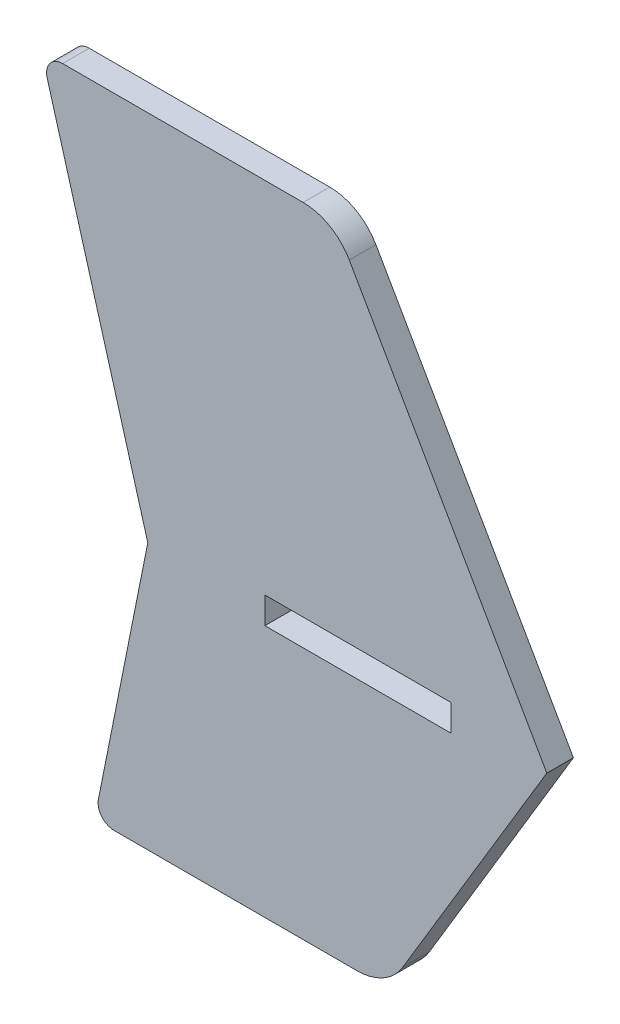
SolidWorks part; units mm, degrees
ref_plane "Ebene vorne" through (0, 0, 0) normal (0, 0, 1) x (1, 0, 0)
ref_plane "Ebene oben" through (0, 0, 0) normal (0, 1, 0) x (1, 0, 0)
ref_plane "Ebene rechts" through (0, 0, 0) normal (1, 0, 0) x (0, 0, -1)
sketch "Skizze1" plane through (0, 0, 0) normal (0, 0, 1) x (1, 0, 0)
  line L1 (-35, 120) -> (20, 120)
  line L2 (20, 120) -> (60, 50)
  line L3 (60, 50) -> (30, 0)
  line L4 (30, 0) -> (0, 0)
  line L5 (-35, 120) -> (-15, 50)
  line L6 (-15, 50) -> (-25, 0)
  line L7 (-25, 0) -> (0, 0)
  dimension "D1" = 120
  dimension "D2" = 55
  dimension "D3" = 30
  dimension "D4" = 40
  dimension "D5" = 50
  dimension "D6" = 30
  dimension "D7" = 25
  dimension "D8" = 75
extrude "Grundplatte" add sketch "Skizze1" along normal blind 5 contours L1 L2 L3 L4 L7 L6 L5
sketch "Skizze2" plane through (0, 0, 5) normal (0, 0, 1) x (1, 0, 0)
  line L1 (7, 47.5) -> (42, 47.5)
  line L2 (7, 47.5) -> (7, 52.5)
  line L3 (7, 52.5) -> (42, 52.5)
  line L4 (42, 47.5) -> (42, 52.5)
  line L5 (42, 50) -> (60, 50) construction
  dimension "D1" = 35
  dimension "D2" = 5
  dimension "D3" = 18
extrude "NutHöhenleitwerk" cut sketch "Skizze2" against normal blind 15
fillet "Verrundung1" radius 10 2 edges at (30, 0, 2.5) (20, 120, 2.5)
fillet "Verrundung2" radius 3 2 edges at (-25, 0, 2.5) (-35, 120, 2.5)
